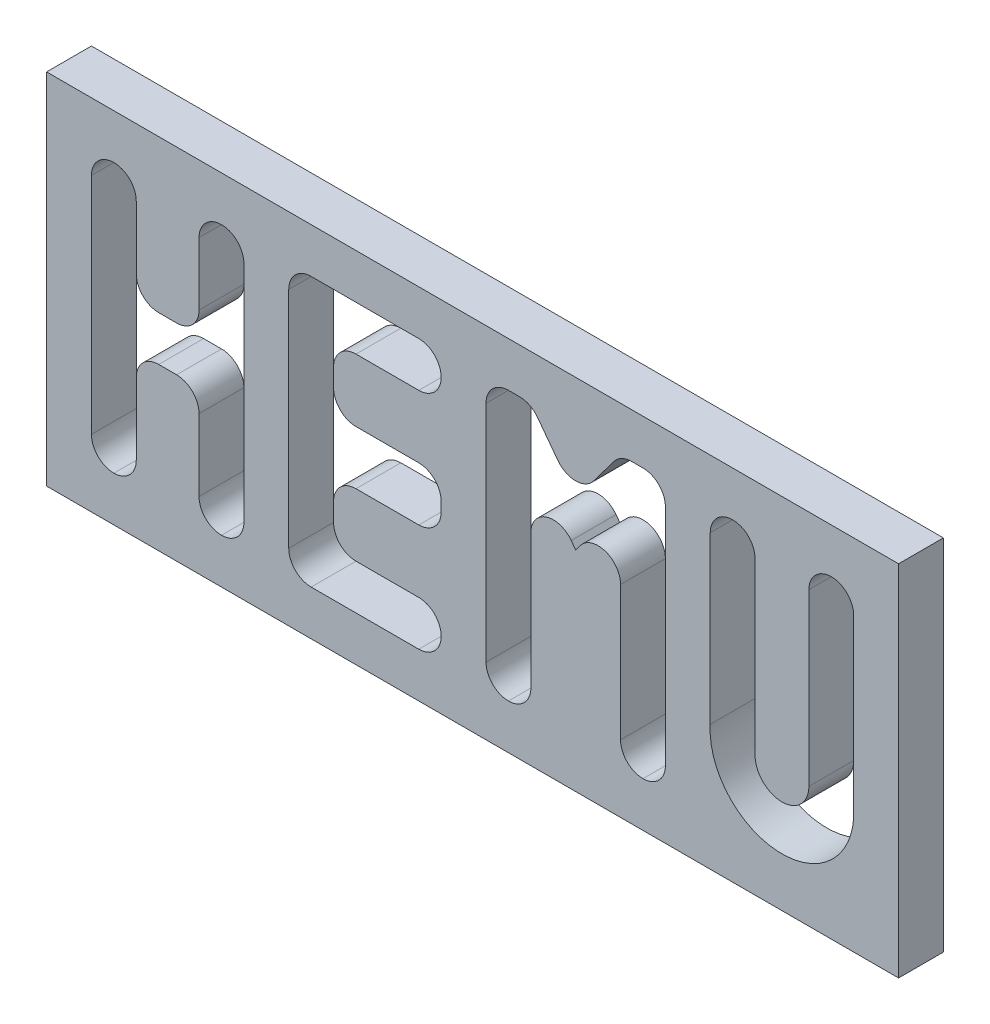
SolidWorks part; units mm, degrees
ref_plane "Front Plane" through (0, 0, 0) normal (0, 0, 1) x (1, 0, 0)
ref_plane "Top Plane" through (0, 0, 0) normal (0, 1, 0) x (1, 0, 0)
ref_plane "Right Plane" through (0, 0, 0) normal (1, 0, 0) x (0, 0, -1)
sketch "Sketch1" plane through (0, 0, 0) normal (0, 0, 1) x (1, 0, 0)
  line L1 (-95, -40) -> (95, -40)
  line L2 (-95, -40) -> (-95, 40)
  line L3 (-95, 40) -> (95, 40)
  line L4 (95, -40) -> (95, 40)
  line L5 (-95, -40) -> (95, 40) construction
  line L6 (-95, 40) -> (95, -40) construction
  point P0 (0, 0)
  dimension "D1" = 190
  dimension "D2" = 80
extrude "Boss-Extrude1" add sketch "Sketch1" along normal blind 10
sketch "Sketch2" plane through (0, 0, 0) normal (0, 0, 1) x (1, 0, 0)
  line L0 (-95, 40) -> (-95, -40) construction
  line L5 (-75, -30) -> (-85, -30)
  line L6 (-75, -30) -> (-75, -4)
  line L7 (-75, 30) -> (-85, 30)
  line L8 (-85, -30) -> (-85, 30)
  line L9 (-31, 20) -> (-31, 6)
  line L11 (-61, 6) -> (-75, 6)
  line L13 (-61, -4) -> (-75, -4)
  line L17 (-51, -30) -> (-61, -30)
  line L18 (-51, -30) -> (-51, 30)
  line L19 (-51, 30) -> (-61, 30)
  line L20 (-61, -30) -> (-61, -4)
  line L22 (-41, -30) -> (-7, -30)
  line L23 (95, 40) -> (-95, 40) construction
  line L24 (-75, 6) -> (-75, 30)
  line L25 (-61, 6) -> (-61, 30)
  line L26 (-41, -30) -> (-41, 30)
  line L27 (-41, 30) -> (-7, 30)
  line L28 (-7, -30) -> (-7, -20)
  line L29 (-7, -6) -> (-7, 6)
  line L30 (-31, -6) -> (-31, -20)
  line L31 (43, -30) -> (33, -30)
  line L32 (43, -30) -> (43, 30)
  line L33 (43, 30) -> (33, 30)
  line L34 (3, -30) -> (3, 30)
  line L35 (13, 20) -> (13, -30)
  line L36 (33, 20) -> (33, -30)
  line L38 (53, -12) -> (53, 30)
  line L39 (53, 30) -> (63, 30)
  line L42 (23, 6.6667) -> (33, 20)
  line L43 (-31, 20) -> (-7, 20)
  line L44 (-31, 6) -> (-7, 6)
  line L45 (-31, -6) -> (-7, -6)
  line L46 (-31, -20) -> (-7, -20)
  line L47 (-7, 20) -> (-7, 30)
  line L48 (13, 20) -> (23, 6.6667)
  line L49 (13, 30) -> (23, 16.6667)
  line L50 (23, 16.6667) -> (33, 30)
  line L51 (3, 30) -> (13, 30)
  line L52 (13, -30) -> (3, -30)
  line L53 (63, 30) -> (63, -13)
  line L56 (95, -40) -> (95, 40) construction
  line L57 (-95, -40) -> (95, -40) construction
  line L60 (75, -13) -> (75, 30)
  line L62 (75, 30) -> (85, 30)
  line L63 (85, 30) -> (85, -12)
  arc A2 (53, -12) -> (85, -12) centre (69, -13) ccw
  arc A3 (63, -13) -> (75, -13) centre (69, -13) ccw
  point P0 (-42.5, 0)
  point P5 (-37.5, 1.0199)
  point P10 (-32.5, -1.613)
  point P19 (-14.5, 0)
  point P24 (7.5, 0)
  point P29 (29.5, 0)
  point P30 (63.0016, -13.1376)
  point P31 (75, -13)
  dimension "D34" = 42
  dimension "D36" = 10
  dimension "D32" = 12
  dimension "D37" = 27
  dimension "D39" = 12
  dimension "D1" = 10
  dimension "D2" = 60
  dimension "D3" = 10
  dimension "D4" = 10
  dimension "D5" = 60
  dimension "D6" = 10
  dimension "D7" = 10
  dimension "D8" = 14
  dimension "D9" = 34
  dimension "D10" = 10
  dimension "D11" = 10
  dimension "D12" = 10
  dimension "D13" = 10
  dimension "D14" = 10
  dimension "D15" = 10
  dimension "D16" = 60
  dimension "D17" = 10
  dimension "D18" = 10
  dimension "D19" = 10
  dimension "D20" = 10
  dimension "D21" = 10
  dimension "D22" = 14
  dimension "D23" = 14
  dimension "D24" = 10
  dimension "D25" = 10
  dimension "D26" = 10
  dimension "D27" = 10
  dimension "D28" = 10
  dimension "D29" = 20
  dimension "D30" = 10
  dimension "D31" = 60
  dimension "D33" = 6
  dimension "D35" = 36.87
  dimension "D38" = 42
extrude "Cut-Extrude1" cut sketch "Sketch2" along normal blind 10 contours L6 L13 L20 L17 L18 L19 L25 L11 L24 L7 L8 L5 | L9 L44 L29 L45 L30 L46 L28 L22 L26 L27 L47 L43 | L42 L36 L31 L32 L33 L50 L49 L51 L34 L52 L35 L48 | L60 L62 L63 A2 L38 L39 L53 A3
fillet "Fillet1" radius 5 39 edges at (-7, 20, 5) (-7, -6, 5) (-75, 6, 5) (-75, -30, 5) (-51, -30, 5) (-7, -30, 5) (43, -30, 5) (13, -30, 5) (-31, -20, 5) (-31, 6, 5) (75, 30, 5) (53, 30, 5) (33, 30, 5) (3, 30, 5) (-85, 30, 5) (-61, 30, 5) (-41, 30, 5) (-7, -20, 5) (23, 16.6667, 5) (13, 30, 5) (43, 30, 5) (85, 30, 5) (63, 30, 5) (-7, 30, 5) (-7, 6, 5) (-75, 30, 5) (-51, 30, 5) (-61, 6, 5) (-61, -30, 5) (-85, -30, 5) (-75, -4, 5) (-61, -4, 5) (-31, 20, 5) (-31, -6, 5) (-41, -30, 5) (33, -30, 5) (3, -30, 5) (13, 20, 5) (33, 20, 5)
